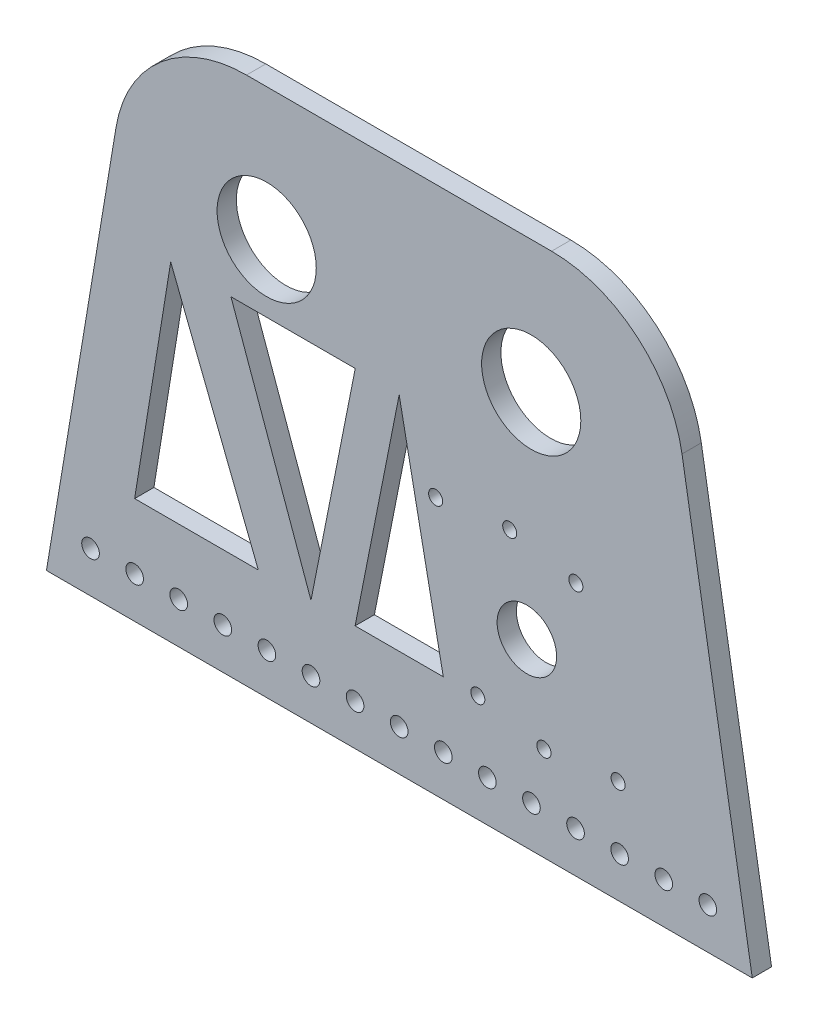
SolidWorks part; units mm, degrees
ref_plane "Front Plane" through (0, 0, 0) normal (0, 0, 1) x (1, 0, 0)
ref_plane "Top Plane" through (0, 0, 0) normal (0, 1, 0) x (1, 0, 0)
ref_plane "Right Plane" through (0, 0, 0) normal (1, 0, 0) x (0, 0, -1)
sketch "Sketch2" plane through (0, 0, 0) normal (0, 0, 1) x (1, 0, 0)
  line L0 (-33.222, -123.0337) -> (-58.5557, -123.0337)
  line L1 (-33.222, 29.3663) -> (119.178, 29.3663)
  line L3 (-33.222, -123.0337) -> (119.178, -123.0337)
  line L5 (-58.5557, -123.0337) -> (-33.222, 29.3663)
  line L6 (119.178, -123.0337) -> (144.7459, -123.0337)
  line L7 (144.7459, -123.0337) -> (119.178, 29.3663)
  line L8 (-22.7678, -28.1678) -> (-33.1557, -92.3946)
  line L9 (-33.1557, -92.3946) -> (2.468, -92.3946)
  line L10 (2.468, -92.3946) -> (-22.7678, -28.1678)
  line L14 (43.0443, -28.3997) -> (55.7443, -92.3946)
  line L15 (55.7443, -92.3946) -> (30.3443, -92.3946)
  line L16 (30.3443, -92.3946) -> (43.0443, -28.3997)
  line L20 (17.6443, -92.3946) -> (30.3903, -28.1678)
  line L21 (30.3903, -28.1678) -> (-5.4154, -28.1678)
  line L22 (-5.4154, -28.1678) -> (17.6443, -92.3946)
  circle A0 centre (4.878, -8.7337) radius 14.2875
  circle A1 centre (81.078, -8.7337) radius 14.2875
  circle A2 centre (-45.8557, -111.1877) radius 2.54
  circle A3 centre (-33.1557, -111.1877) radius 2.54
  circle A4 centre (-20.4557, -111.1877) radius 2.54
  circle A5 centre (-7.7557, -111.1877) radius 2.54
  circle A6 centre (4.9443, -111.1877) radius 2.54
  circle A7 centre (17.6443, -111.1877) radius 2.54
  circle A8 centre (30.3443, -111.1877) radius 2.54
  circle A9 centre (43.0443, -111.1877) radius 2.54
  circle A10 centre (55.7443, -111.1877) radius 2.54
  circle A11 centre (68.4443, -111.1877) radius 2.54
  circle A12 centre (81.1443, -111.1877) radius 2.54
  circle A13 centre (93.8443, -111.1877) radius 2.54
  circle A14 centre (106.5443, -111.1877) radius 2.54
  circle A15 centre (119.2443, -111.1877) radius 2.54
  circle A16 centre (131.9443, -111.1877) radius 2.54
  circle A17 centre (106.0951, -93.3478) radius 2.0193
  circle A18 centre (53.5442, -48.7401) radius 2.0193
  circle A19 centre (84.7428, -95.9685) radius 2.0429
  circle A20 centre (65.6988, -92.1571) radius 2.0193
  circle A21 centre (74.8753, -46.1298) radius 2.0193
  circle A22 centre (93.9404, -49.9309) radius 2.0193
  circle A23 centre (79.8188, -71.0396) radius 8.5708
  dimension "D3" = 28.575
  dimension "D4" = 28.575
  dimension "D9" = 15
  dimension "D10" = 12.7
  dimension "D1" = 152.4
  dimension "D2" = 152.4
  dimension "D5" = 76.2
  dimension "D6" = 38.1
  dimension "D7" = 38.1
  dimension "D8" = 38.1
extrude "Boss-Extrude1" add sketch "Sketch2" along normal blind 5.5562
fillet "Fillet1" radius 38.1 2 edges at (-33.222, 29.3663, 2.7781) (119.178, 29.3663, 2.7781)
